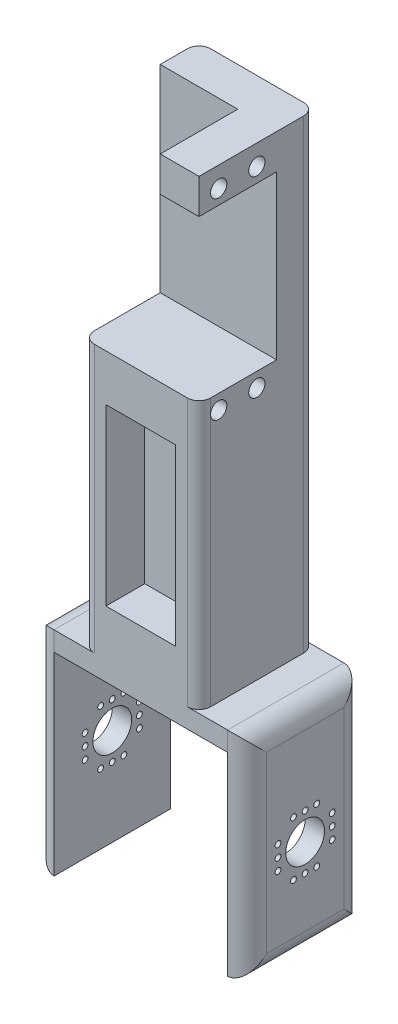
SolidWorks part; units mm, degrees
material "1023 碳钢板 (SS)"
ref_plane "前视基准面" through (0, 0, 0) normal (0, 0, 1) x (1, 0, 0)
ref_plane "上视基准面" through (0, 0, 0) normal (0, 1, 0) x (1, 0, 0)
ref_plane "右视基准面" through (0, 0, 0) normal (1, 0, 0) x (0, 0, -1)
other "Configuration Table"
sketch "草图1" plane through (0, 0, 0) normal (0, 0, 1) x (1, 0, 0)
  line L1 (-22.375, 25) -> (22.375, 25)
  line L2 (-22.375, 25) -> (-22.375, -25)
  line L3 (-22.375, -25) -> (22.375, -25)
  line L4 (22.375, 25) -> (22.375, -25)
  line L5 (-22.375, 25) -> (22.375, -25) construction
  line L6 (-22.375, -25) -> (22.375, 25) construction
  point P0 (0, 0)
extrude "凸台-拉伸1" add sketch "草图1" along normal blind 30
shell "抽壳1" thickness 5 removed face at (0, 0, 0) removed face at (0, -25, 15) removed face at (0, 0, 30) outward yes
fillet "圆角1" radius 5 8 edges at (-27.375, 30, 15) (-27.375, 2.5, 30) (-27.375, -25, 15) (-27.375, 2.5, 0) (27.375, -25, 15) (27.375, 2.5, 30) (27.375, 30, 15) (27.375, 2.5, 0)
sketch "草图2" plane through (-27.375, 0, 0) normal (-1, 0, 0) x (0, 0, 1)
  circle A0 centre (15, 7) radius 0.75
  circle A1 centre (12, 7) radius 0.75
  circle A3 centre (18, 7) radius 0.75
  circle A5 centre (8, -3) radius 0.75
  circle A6 centre (8, 0) radius 0.75
  circle A7 centre (8, 3) radius 0.75
  circle A8 centre (12, -7) radius 0.75
  circle A9 centre (15, -7) radius 0.75
  circle A10 centre (18, -7) radius 0.75
  circle A11 centre (22, -3) radius 0.75
  circle A12 centre (22, 0) radius 0.75
  circle A13 centre (22, 3) radius 0.75
extrude "切除-拉伸1" cut sketch "草图2" against normal through all
sketch "草图3" plane through (27.375, 0, 0) normal (1, 0, 0) x (0, 0, -1)
  circle A0 centre (-15, 0) radius 5
extrude "切除-拉伸2" cut sketch "草图3" against normal through all
sketch "草图4" plane through (0, 0, 30) normal (0, 0, 1) x (1, 0, 0)
  line L0 (0, 30) -> (-15, 30)
  line L5 (22.375, 30) -> (-22.375, 30) construction
  line L6 (-15, 30) -> (-15, 150)
  line L7 (-15, 150) -> (15, 150)
  line L8 (15, 150) -> (15, 30)
  line L9 (15, 30) -> (0, 30)
extrude "凸台-拉伸2" add sketch "草图4" against normal blind 30
sketch "草图6" plane through (0, 0, 30) normal (0, 0, 1) x (1, 0, 0)
  line L1 (-15, 150) -> (-15, 30) construction
  line L2 (-15, 99) -> (15, 99)
  line L3 (15, 30) -> (15, 150) construction
  line L5 (15, 150) -> (-15, 150) construction
  line L9 (5, 141) -> (5, 150)
  line L12 (-15, 141) -> (-15, 99)
  line L13 (5, 150) -> (-15, 150)
  line L14 (-15, 150) -> (-15, 141)
  line L15 (5, 141) -> (15, 141)
  line L16 (15, 141) -> (15, 99)
extrude "切除-拉伸3" cut sketch "草图6" against normal blind 20
sketch "草图7" plane through (15, 0, 0) normal (1, 0, 0) x (0, 0, -1)
  circle A0 centre (-24.925, 144.75) radius 2.1
  circle A1 centre (-15.075, 144.75) radius 2.1
  circle A4 centre (-15.075, 95.25) radius 2.1
  circle A5 centre (-24.925, 95.25) radius 2.1
  dimension "D1" = 49.5
  dimension "D2" = 49.5
extrude "切除-拉伸4" cut sketch "草图7" against normal through all
sketch "草图8" plane through (0, 0, 30) normal (0, 0, 1) x (1, 0, 0)
  line L1 (-9, 87) -> (9, 87)
  line L4 (-9, 87) -> (-9, 42)
  line L5 (-9, 42) -> (9, 42)
  line L6 (9, 87) -> (9, 42)
  line L7 (-9, 87) -> (9, 42) construction
  line L8 (-9, 42) -> (9, 87) construction
extrude "切除-拉伸5" cut sketch "草图8" against normal blind 10
sketch "草图9" plane through (0, 0, 0) normal (0, 0, -1) x (-1, 0, 0)
  line L8 (-9, 87.5) -> (9, 87.5)
  line L9 (-9, 87.5) -> (-9, 42.5)
  line L10 (-9, 42.5) -> (9, 42.5)
  line L11 (9, 87.5) -> (9, 42.5)
  line L12 (-9, 87.5) -> (9, 42.5) construction
  line L13 (-9, 42.5) -> (9, 87.5) construction
extrude "切除-拉伸6" cut sketch "草图9" against normal blind 10
fillet "圆角2" radius 3 4 edges at (15, 90, 0) (-15, 90, 0) (-15, 64.5, 30) (15, 64.5, 30)
